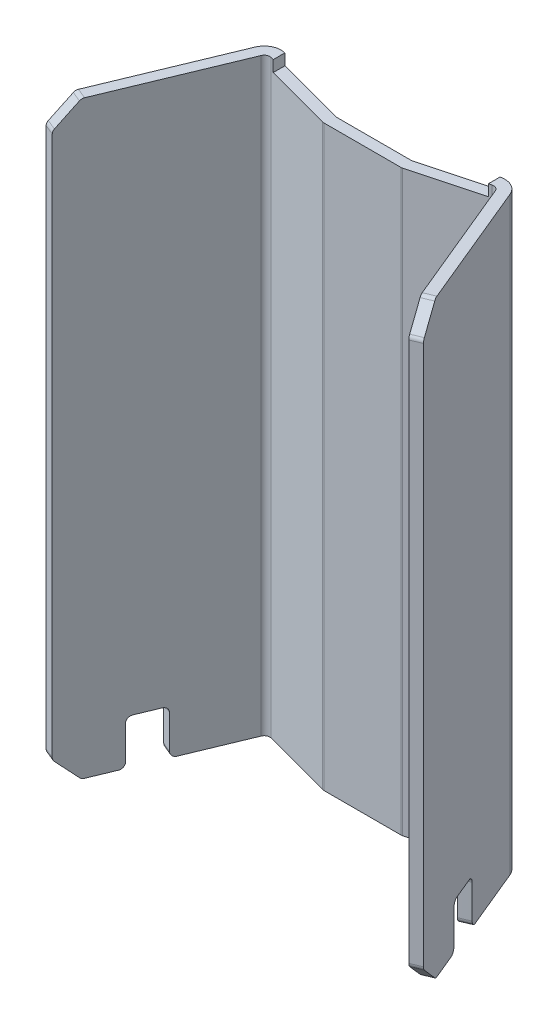
SolidWorks part; units mm, degrees
ref_plane "Front Plane" through (0, 0, 0) normal (0, 0, 1) x (1, 0, 0)
ref_plane "Top Plane" through (0, 0, 0) normal (0, 1, 0) x (1, 0, 0)
ref_plane "Right Plane" through (0, 0, 0) normal (1, 0, 0) x (0, 0, -1)
sketch "Sketch3" plane through (0, 0, 0) normal (0, 1, 0) x (1, 0, 0)
  line L0 (0, 0) -> (0, -85) construction
  line L1 (0, 0) -> (-32.5281, -78.5298) construction
  line L2 (0, 0) -> (32.5281, -78.5298) construction
  line L3 (-20.523, -49.5468) -> (-7, -53.1703)
  line L4 (20.523, -49.5468) -> (7, -53.1703)
  line L5 (-7, -53.1703) -> (7, -53.1703)
  line L6 (-20.523, -49.5468) -> (-31.7627, -76.682)
  line L7 (20.523, -49.5468) -> (31.7627, -76.682)
  line L8 (-31.7627, -76.682) -> (-32.5281, -78.5298) construction
  line L9 (31.7627, -76.682) -> (32.5281, -78.5298) construction
  line L10 (-21.6995, -47.161) -> (-33.6105, -75.9166)
  line L11 (-21.6995, -47.161) -> (-6.7367, -51.1703)
  line L12 (-6.7367, -51.1703) -> (6.7367, -51.1703)
  line L13 (21.6995, -47.161) -> (6.7367, -51.1703)
  line L14 (21.6995, -47.161) -> (33.6105, -75.9166)
  line L15 (-31.7627, -76.682) -> (-33.6105, -75.9166)
  line L16 (31.7627, -76.682) -> (33.6105, -75.9166)
  circle A0 centre (0, 0) radius 85 construction
  circle A1 centre (0, 0) radius 53.1703 construction
  circle A2 centre (0, 0) radius 25 construction
  dimension "D1" = 170
  dimension "D2" = 14
  dimension "D4" = 50
  dimension "D3" = 45
  dimension "D5" = 2
  dimension "D6" = 2
extrude "Boss-Extrude2" add sketch "Sketch3" along normal blind 105
ref_axis "Axis1" through (0, 115.5, 0) along (0, -1, 0)
sketch "Sketch4" plane through (0, 0, 0) normal (0, -1, 0) x (1, 0, 0)
  line L12 (-20.523, 49.5468) -> (-31.7627, 76.682)
  line L13 (-31.7627, 76.682) -> (-33.6105, 75.9166)
  line L14 (-33.6105, 75.9166) -> (-21.6995, 47.161)
  line L15 (-21.6995, 47.161) -> (-6.7367, 51.1703)
  line L16 (-6.7367, 51.1703) -> (6.7367, 51.1703)
  line L17 (6.7367, 51.1703) -> (21.6995, 47.161)
  line L18 (21.6995, 47.161) -> (33.6105, 75.9166)
  line L19 (33.6105, 75.9166) -> (31.7627, 76.682)
  line L20 (31.7627, 76.682) -> (20.523, 49.5468)
  line L21 (20.523, 49.5468) -> (7, 53.1703)
  line L22 (7, 53.1703) -> (-7, 53.1703)
  line L23 (-7, 53.1703) -> (-20.523, 49.5468)
  line L24 (-25.6398, 61.8999) -> (-27.9359, 67.4432)
  line L25 (-31.7627, 76.682) -> (-33.6105, 75.9166)
  line L26 (-29.7732, 66.6525) -> (-27.4761, 61.107)
  line L30 (27.4761, 61.107) -> (33.6105, 75.9166)
  line L31 (33.6105, 75.9166) -> (31.7627, 76.682)
  line L32 (31.7627, 76.682) -> (25.6398, 61.8999)
  circle A0 centre (0, 0) radius 70 construction
  arc A1 (29.7732, 66.6525) -> (27.9359, 67.4432) centre (0, 0) ccw
  arc A2 (27.4761, 61.107) -> (25.6398, 61.8999) centre (0, 0) ccw
  circle A3 centre (0, 0) radius 73 construction
  circle A4 centre (0, 0) radius 67 construction
  arc A5 (-25.6398, 61.8999) -> (-27.4761, 61.107) centre (0, 0) ccw
  arc A6 (-27.9359, 67.4432) -> (-29.7732, 66.6525) centre (0, 0) ccw
  line M14 (-20.523, 49.5468) -> (-31.7627, 76.682)
  line M16 (-33.6105, 75.9166) -> (-21.6995, 47.161)
  line M20 (21.6995, 47.161) -> (33.6105, 75.9166)
  dimension "D1" = 140
  dimension "D2" = 3
  dimension "D3" = 3
  dimension "D4" = 0
extrude "Cut-Extrude1" cut sketch "Sketch4" against normal blind 8 contours A6 A5 M14 M16 | A2 A1 L32 M20 region at (-27.7081, 0, 64.28) region at (27.7081, 0, 64.28)
fillet "Fillet1" radius 4 4 edges at (32.6866, 0, 76.2993) (-32.6866, 0, 76.2993) (32.6866, 105, 76.2993) (-32.6866, 105, 76.2993) profile chamfer
fillet "Fillet2" radius 1 16 edges at (28.8572, 0, 67.0542) (26.5609, 0, 61.5103) (26.5609, 8, 61.5103) (28.8572, 8, 67.0542) (-28.8572, 0, 67.0542) (-28.8572, 8, 67.0542) (-26.5609, 0, 61.5103) (-26.5609, 8, 61.5103) (-32.6866, 4, 76.2993) (-31.1559, 0, 72.6038) (31.1559, 0, 72.6038) (32.6866, 4, 76.2993) (32.6866, 101, 76.2993) (31.1559, 105, 72.6038) (-31.1559, 105, 72.6038) (-32.6866, 101, 76.2993)
fillet "Fillet3" radius 1 6 edges at (-20.523, 52.5, 49.5468) (20.523, 52.5, 49.5468) (6.7367, 52.5, 51.1703) (-6.7367, 52.5, 51.1703) (7, 52.5, 53.1703) (-7, 52.5, 53.1703)
fillet "Fillet4" radius 3 2 edges at (21.6995, 52.5, 47.161) (-21.6995, 52.5, 47.161)
ref_plane "Plane1" through (0, 24, 0) normal (0, 1, 0) x (1, 0, 0)
sketch "Sketch5" plane through (0, 24, 0) normal (0, 1, 0) x (1, 0, 0)
  line L0 (0, 0) -> (0, -46) construction
  line L1 (10, -48) -> (-10, -48)
  line L2 (10, -48) -> (10, -44)
  line L3 (10, -44) -> (-10, -44)
  line L4 (-10, -48) -> (-10, -44)
  line L5 (10, -48) -> (-10, -44) construction
  line L6 (10, -44) -> (-10, -48) construction
  line L7 (-19.1582, -47.8419) -> (-6.8639, -51.1362)
  line L8 (-19.1582, -47.8419) -> (-6.8639, -51.1362)
  line L9 (-6.605, -51.1703) -> (6.605, -51.1703)
  line L10 (-6.605, -51.1703) -> (6.605, -51.1703)
  line L11 (6.8639, -51.1362) -> (19.1582, -47.8419)
  line L12 (6.8639, -51.1362) -> (19.1582, -47.8419)
  line L13 (-19.1582, -47.8419) -> (-13.3163, -42)
  line L14 (19.1582, -47.8419) -> (13.3163, -42)
  line L15 (-13.3163, -42) -> (13.3163, -42)
  arc A0 (6.605, -51.1703) -> (6.8639, -51.1362) centre (6.605, -50.1703) ccw
  arc A1 (6.605, -51.1703) -> (6.8639, -51.1362) centre (6.605, -50.1703) ccw
  arc A2 (-6.8639, -51.1362) -> (-6.605, -51.1703) centre (-6.605, -50.1703) ccw
  arc A3 (-6.8639, -51.1362) -> (-6.605, -51.1703) centre (-6.605, -50.1703) ccw
  arc A4 (-19.1582, -47.8419) -> (-22.7063, -49.5917) centre (-19.9347, -50.7397) ccw
  arc A5 (-19.1582, -47.8419) -> (-22.7063, -49.5917) centre (-19.9347, -50.7397) ccw
  arc A6 (22.7063, -49.5917) -> (19.1582, -47.8419) centre (19.9347, -50.7397) ccw
  arc A7 (22.7063, -49.5917) -> (19.1582, -47.8419) centre (19.9347, -50.7397) ccw
  point P0 (0, -46)
  point P23 (0, -42)
  dimension "D1" = 46
  dimension "D2" = 4
  dimension "D3" = 20
  dimension "D4" = 2
  dimension "D5" = 45
extrude "Boss-Extrude3" add sketch "Sketch5" against normal up to surface (24 mm away) contours L8 A3 L10 A1 L12 L14 L15 L13 L1 L4 L3 L2 region at (-15.9587, 24, 45.1996) up to face at (0, 0, 52.647)
fillet "Fillet5" radius 3 4 edges at (-19.1582, 12, 47.8419) (-13.3163, 12, 42) (19.1582, 12, 47.8419) (13.3163, 12, 42)
chamfer "Chamfer1" distance 0.5 angle 45 4 edges at (10, 24, 46) (0, 24, 44) (-10, 24, 46) (0, 24, 48)
chamfer "Chamfer2" distance 0.5 angle 45 7 edges at (-19.6365, 24, 47.7546) (-13.011, 24, 49.4891) (-6.7356, 24, 51.1617) (0, 24, 51.1703) (6.7356, 24, 51.1617) (19.6365, 24, 47.7546) (13.011, 24, 49.4891)
sketch "Sketch6" plane through (0, 0, 51.1703) normal (0, 0, -1) x (-1, 0, 0)
  line L0 (-19.1582, 105) -> (-6.8639, 105) construction
  line L1 (-19.1582, 105) -> (19.1582, 105)
  line L2 (-19.1582, 105) -> (-19.1582, 103)
  line L3 (-19.1582, 103) -> (19.1582, 103)
  line L4 (19.1582, 105) -> (19.1582, 103)
  line L5 (19.1582, 24.5) -> (19.1582, 105) construction
  line L6 (-19.1582, 105) -> (-19.1582, 24.5) construction
  point P8 (-19.1582, 101.1312)
  dimension "D1" = 2
extrude "Cut-Extrude2" cut sketch "Sketch6" against normal through all both and the other way through all
